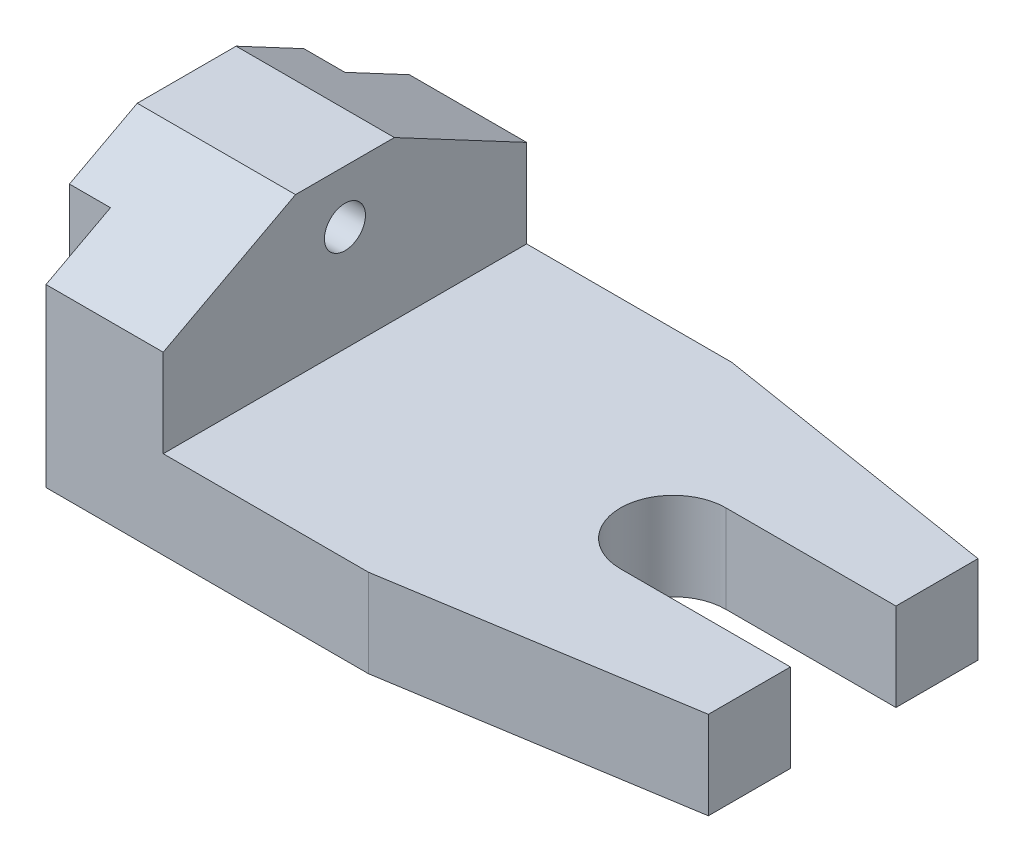
SolidWorks part; units mm, degrees
ref_plane "Front Plane" through (0, 0, 0) normal (0, 0, 1) x (1, 0, 0)
ref_plane "Top Plane" through (0, 0, 0) normal (0, 1, 0) x (1, 0, 0)
ref_plane "Right Plane" through (0, 0, 0) normal (1, 0, 0) x (0, 0, -1)
sketch "Sketch1" plane through (0, 0, 0) normal (0, 1, 0) x (1, 0, 0)
  line L0 (0, 20) -> (0, -20)
  line L4 (27, -31) -> (27, 31)
  line L5 (27, 31) -> (7, 31)
  line L6 (7, 31) -> (7, 20)
  line L7 (7, 20) -> (0, 20)
  line L8 (27, 31) -> (62, 31)
  line L9 (62, 31) -> (112, 23)
  line L10 (112, 23) -> (112, 9)
  line L11 (112, 9) -> (83, 9)
  line L12 (-8.6301, 0) -> (166.6849, 0) construction
  line L13 (112, -9) -> (83, -9)
  line L14 (112, -23) -> (112, -9)
  line L15 (62, -31) -> (112, -23)
  line L16 (27, -31) -> (62, -31)
  line L17 (7, -20) -> (0, -20)
  line L18 (7, -31) -> (7, -20)
  line L19 (27, -31) -> (7, -31)
  arc A0 (83, 9) -> (83, -9) centre (83, 0) ccw
  point P6 (0, 0)
  point P11 (112, 31)
  point P15 (0, 0)
  point P16 (31.8082, 0)
  point P17 (107.5068, 0)
  point P18 (155.9979, 41.0548)
  point P19 (102.3658, 41.0548)
  point P20 (80.5408, 40.5535)
  point P21 (117.5926, 36.6622)
  point P22 (117.5926, 37.339)
  point P24 (112, -31)
  point P33 (27, 0)
  dimension "D1" = 18
  dimension "D2" = 29
  dimension "D3" = 50
  dimension "D4" = 8
  dimension "D5" = 11
  dimension "D6" = 7
  dimension "D7" = 27
  dimension "D8" = 112
  dimension "D9" = 31
extrude "Boss-Extrude1" add sketch "Sketch1" along normal blind 15 contours L12 L4 L16 L15 L14 L13 A0 | L4 L12 A0 L11 L10 L9 L8 region at (63.2971, 0, 15.9963) region at (63.2971, 0, -15.9963)
extrude "Boss-Extrude2" add sketch "Sketch1<3>" along normal blind 42 contours L0 L12 L4 L5 L6 L7 | L12 L0 L17 L18 L19 L4 region at (14.5132, 0, -14.4868) region at (14.5132, 0, 14.4868)
sketch "Sketch1<3>" plane through (0, 0, 0) normal (0, 1, 0) x (1, 0, 0) same geometry as "Sketch1"
sketch "Sketch2" plane through (27, 0, 0) normal (1, 0, 0) x (0, 0, -1)
  line L0 (8.4313, 42) -> (-8.4313, 42)
  line L1 (-31, 42) -> (31, 42) construction
  line L2 (-8.4313, 42) -> (-31, 30)
  line L3 (-31, 42) -> (-31, 15) construction
  line L4 (-31, 30) -> (-31, 15)
  line L5 (-31, 15) -> (31, 15)
  line L6 (9, 15) -> (-9, 15) construction
  line L7 (0, -1.8169) -> (0, 3.8458) construction
  line L8 (31, 30) -> (31, 15)
  line L9 (8.4313, 42) -> (31, 30)
  circle A0 centre (0, 33) radius 3.5
  point P2 (0, 0)
  point P18 (0, 15)
  point P20 (0, 42)
  point P21 (0, 0)
  line M8 (-31, 42) -> (-31, 15)
  line M10 (31, 15) -> (31, 42)
  line M11 (31, 42) -> (-31, 42)
  dimension "D1" = 28
  dimension "D4" = 7
  dimension "D2" = 9
  dimension "D3" = 12
extrude "Cut-Extrude1" cut sketch "Sketch2" against normal up to next contours A0 | L2 M11 M8 | L9 M11 M10 region at (27, 38, -23.4771) region at (27, 38, 23.4771) region at (27, 33, 0)
